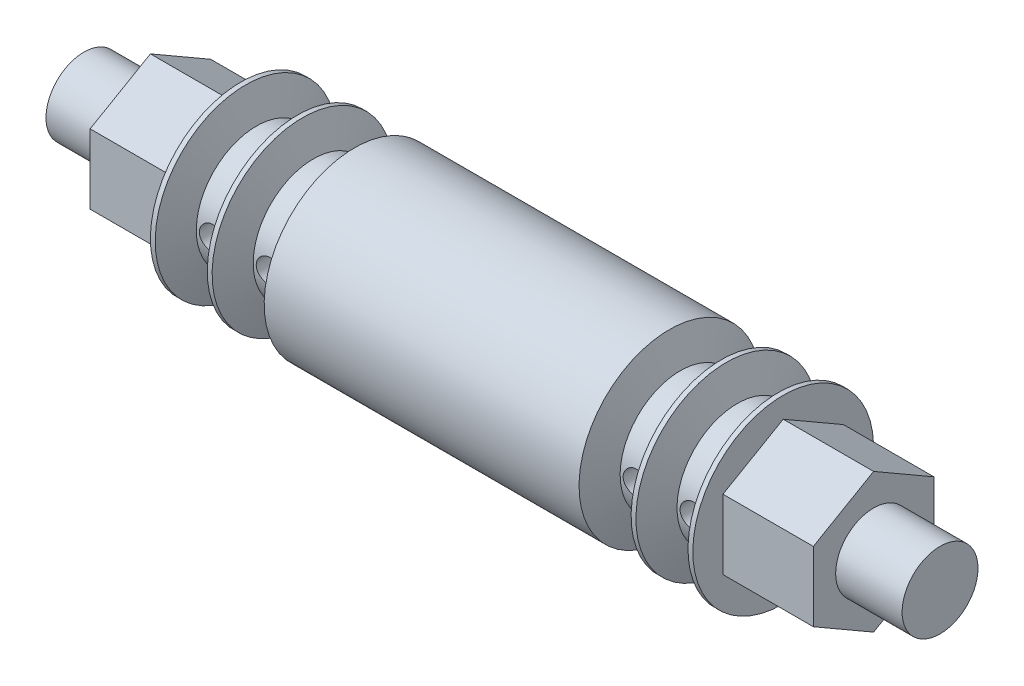
SolidWorks part; units mm, degrees
ref_plane "Front Plane" through (0, 0, 0) normal (0, 0, 1) x (1, 0, 0)
ref_plane "Top Plane" through (0, 0, 0) normal (0, 1, 0) x (1, 0, 0)
ref_plane "Right Plane" through (0, 0, 0) normal (1, 0, 0) x (0, 0, -1)
sketch "Sketch1" plane through (0, 0, 0) normal (0, 0, 1) x (1, 0, 0)
  line L0 (-38.1, 0) -> (38.1, 0) construction
  line L1 (-28.067, 9.525) -> (-26.9114, 6.35)
  line L2 (-26.9114, 6.35) -> (-23.7364, 6.35)
  line L3 (-23.7364, 6.35) -> (-22.5808, 9.525)
  line L4 (-22.5808, 9.525) -> (-22.0728, 9.525)
  line L5 (-22.0728, 9.525) -> (-20.9172, 6.35)
  line L6 (-20.9172, 6.35) -> (-17.7422, 6.35)
  line L7 (-17.7422, 6.35) -> (-16.5866, 9.525)
  line L8 (0, 0) -> (0, 25.6809) construction
  line L9 (-16.5866, 9.525) -> (0, 9.525)
  line L10 (-22.3268, 9.525) -> (-22.3268, 0) construction
  line L11 (-28.575, 9.525) -> (-28.575, 4.254)
  line L12 (-28.575, 4.254) -> (-38.1, 4.254)
  line L13 (-38.1, 4.254) -> (-38.1, 4)
  line L14 (-38.1, 0) -> (-28.575, 0)
  line L15 (-28.575, 0) -> (0, 0)
  line L16 (-28.067, 9.525) -> (-28.575, 9.525)
  line L17 (0, 0) -> (0, 9.525)
  line L18 (-38.1, 0) -> (-38.1, -4) construction
  line L19 (-28.575, 4.254) -> (-28.575, 0) construction
  line L20 (-45.1, 4) -> (-45.1, 0)
  line L21 (-45.1, 4) -> (-38.1, 4)
  line L22 (-45.1, 0) -> (-45.1, -4) construction
  line L23 (-38.1, 4) -> (-38.1, 0) construction
  line L24 (-38.1, 0) -> (-45.1, 0)
  dimension "D2" = 3.175
  dimension "D3" = 3.175
  dimension "D4" = 70
  dimension "D5" = 0.508
  dimension "D6" = 3.175
  dimension "D7" = 3.175
  dimension "D8" = 0.508
  dimension "D9" = 76.2
  dimension "D10" = 0.254
  dimension "D11" = 9.525
  dimension "D12" = 8
  dimension "D13" = 7
  dimension "D14" = 9.525
revolve "Revolve1" add sketch "Sketch1" angle 360 about L0
sketch "Sketch4" plane through (-28.575, 0, 0) normal (-1, 0, 0) x (0, 0, 1)
  line L1 (0, 7.3323) -> (-6.35, 3.6662)
  line L2 (-6.35, 3.6662) -> (-6.35, -3.6662)
  line L3 (-6.35, -3.6662) -> (0, -7.3323)
  line L4 (0, -7.3323) -> (6.35, -3.6662)
  line L5 (6.35, -3.6662) -> (6.35, 3.6662)
  line L6 (6.35, 3.6662) -> (0, 7.3323)
  circle A0 centre (0, 0) radius 6.35 construction
  dimension "D1" = 12.7
extrude "Boss-Extrude4" add sketch "Sketch4" along normal up to surface (9.525 mm away) up to face at (-38.1, -4, 0)
sketch "Sketch6" plane through (0, 0, 0) normal (0, 0, 1) x (1, 0, 0)
  line L0 (-25.3239, 6.35) -> (-25.3239, 0) construction
  line L1 (-26.9114, 6.35) -> (-23.7364, 6.35) construction
  line L2 (-19.3297, 6.35) -> (-19.3297, 0) construction
  line L3 (-20.9172, 6.35) -> (-17.7422, 6.35) construction
  line L4 (-28.575, 0) -> (0, 0) construction
  circle A0 centre (-25.3239, 0) radius 1.27
  circle A1 centre (-19.3297, 0) radius 1.27
  point P0 (-25.3239, 0)
  point P2 (-25.4898, 4.7292)
  point P12 (-19.1951, 4.539)
  point P13 (-19.3297, 4.357)
  dimension "D1" = 2.54
extrude "Cut-Extrude1" cut sketch "Sketch6" against normal through all both and the other way through all
mirror "Mirror1" about plane through (0, 0, 0) normal (1, 0, 0) of "Cut-Extrude1", "Revolve1", "Boss-Extrude4"
